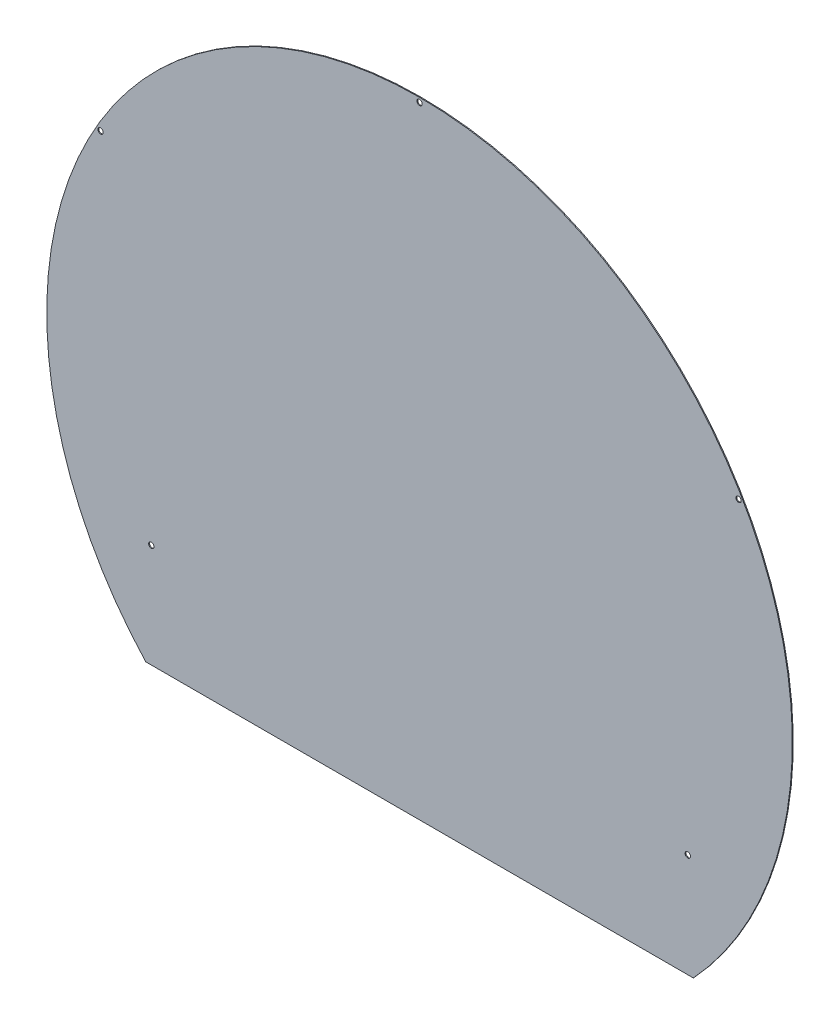
SolidWorks part; units mm, degrees
ref_plane "Спереди" through (0, 0, 0) normal (0, 0, 1) x (1, 0, 0)
ref_plane "Сверху" through (0, 0, 0) normal (0, 1, 0) x (1, 0, 0)
ref_plane "Справа" through (0, 0, 0) normal (1, 0, 0) x (0, 0, -1)
sketch "Эскиз1" plane through (0, 0, 0) normal (0, 0, 1) x (1, 0, 0)
  line L0 (-306.2679, 0) -> (306.2679, 0)
  arc A0 (-306.2679, 0) -> (306.2679, 0) centre (0, 283) cw
  dimension "D1" = 417
  dimension "D2" = 700
sheet metal parameters "Листовой металл1" thickness 1 parameters "D1"=5, "Толщина"=1
base flange "Базовая кромка1" sketch "Эскиз1" thickness 1 reverse thickness direction no parameters "D1"=5
sketch "Эскиз2" plane through (0, 0, 0) normal (0, 0, 1) x (1, 0, 0)
  line L0 (-393.5, 126.0836) -> (393.5, 126.0836) construction
  line L1 (-300, 116.0836) -> (-382.136, 116.0836) construction
  line L2 (300, 116.0836) -> (382.136, 116.0836) construction
  line L3 (0, 700) -> (0, 695) construction
  line L4 (0, 283) -> (356.8025, 489) construction
  line L5 (0, 283) -> (412, 283) construction
  line L6 (0, 283) -> (-356.8025, 489) construction
  circle A0 centre (-300, 116.0836) radius 3
  circle A1 centre (300, 116.0836) radius 3
  circle A2 centre (0, 695) radius 3
  arc A3 (306.2679, 0) -> (-306.2679, 0) centre (0, 283) ccw construction
  circle A4 centre (0, 283) radius 412 construction
  circle A5 centre (356.8025, 489) radius 3
  circle A6 centre (-356.8025, 489) radius 3
  dimension "D2" = 600
  dimension "D3" = 6
  dimension "D1" = 10
  dimension "D4" = 5
  dimension "D5" = 30
  dimension "D6" = 150
extrude "Вырез-Вытянуть1" cut sketch "Эскиз2" against normal through all normal cut yes
flat pattern "Развертка1" [suppressed]
sketch "Сгиб-Линии1" plane through (0, 0, 0) normal (0, 1, 0) x (-1, 0, 0)
equation "\"D6@Эскиз2\" = 180-\"D5@Эскиз2\""
